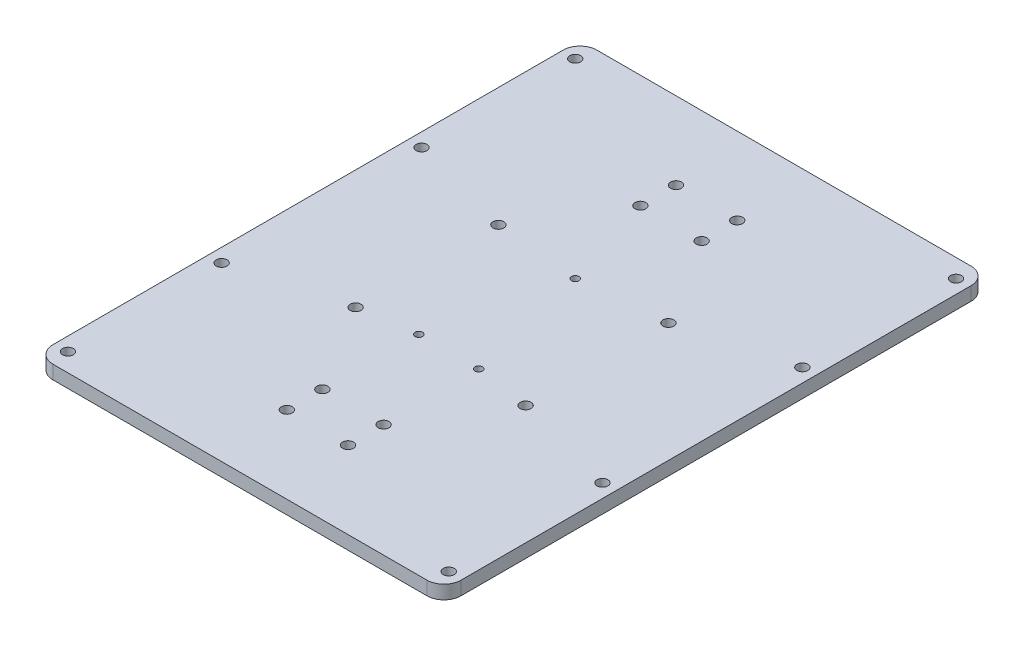
SolidWorks part; units mm, degrees
material "自定义塑料"
ref_plane "前视基准面" through (0, 0, 0) normal (0, 0, 1) x (1, 0, 0)
ref_plane "上视基准面" through (0, 0, 0) normal (0, 1, 0) x (1, 0, 0)
ref_plane "右视基准面" through (0, 0, 0) normal (1, 0, 0) x (0, 0, -1)
sketch "草图1" plane through (0, 0, 0) normal (0, 1, 0) x (1, 0, 0)
  line L0 (0, 0) -> (-20.2314, 0) construction
  line L1 (-60, 80) -> (60, 80)
  line L2 (-60, 80) -> (-60, -80)
  line L3 (-60, -80) -> (60, -80)
  line L4 (60, 80) -> (60, -80)
  line L5 (-60, 80) -> (60, -80) construction
  line L6 (-60, -80) -> (60, 80) construction
  line L7 (0, 0) -> (0, 21.0425) construction
  line L8 (-60, 52) -> (-53.3899, 52) construction
  circle A0 centre (-56, 74.6) radius 1.6
  circle A1 centre (-56, 29.4) radius 1.6
  circle A2 centre (-9, 57.23) radius 1.6
  circle A3 centre (-9, 46.77) radius 1.6
  circle A4 centre (-56, -29.4) radius 1.6
  circle A5 centre (-9, -46.77) radius 1.6
  circle A6 centre (-9, -57.23) radius 1.6
  circle A7 centre (-56, -74.6) radius 1.6
  circle A8 centre (56, -74.6) radius 1.6
  circle A9 centre (9, -57.23) radius 1.6
  circle A10 centre (9, -46.77) radius 1.6
  circle A11 centre (56, -29.4) radius 1.6
  circle A12 centre (56, 29.4) radius 1.6
  circle A13 centre (9, 46.77) radius 1.6
  circle A14 centre (9, 57.23) radius 1.6
  circle A15 centre (56, 74.6) radius 1.6
  circle A16 centre (0, 18.6) radius 1.1
  circle A17 centre (8.8, -18.6) radius 1.1
  circle A18 centre (-8.8, -18.6) radius 1.1
  circle A19 centre (-25, 21) radius 1.6
  circle A20 centre (25, 21) radius 1.6
  circle A21 centre (25, -21) radius 1.6
  circle A22 centre (-25, -21) radius 1.6
  point P0 (0, 0)
  dimension "D4" = 3.2
  dimension "D9" = 2.2
  dimension "D15" = 3.2
  dimension "D1" = 120
  dimension "D2" = 160
  dimension "D3" = 52
  dimension "D5" = 45.2
  dimension "D6" = 4
  dimension "D7" = 10.46
  dimension "D8" = 47
  dimension "D10" = 18.6
  dimension "D11" = 18.6
  dimension "D12" = 8.8
  dimension "D13" = 50
  dimension "D14" = 42
extrude "凸台-拉伸1" add sketch "草图1" along normal blind 4
fillet "圆角1" radius 5 4 edges at (-60, 2, -80) (60, 2, -80) (60, 2, 80) (-60, 2, 80)
